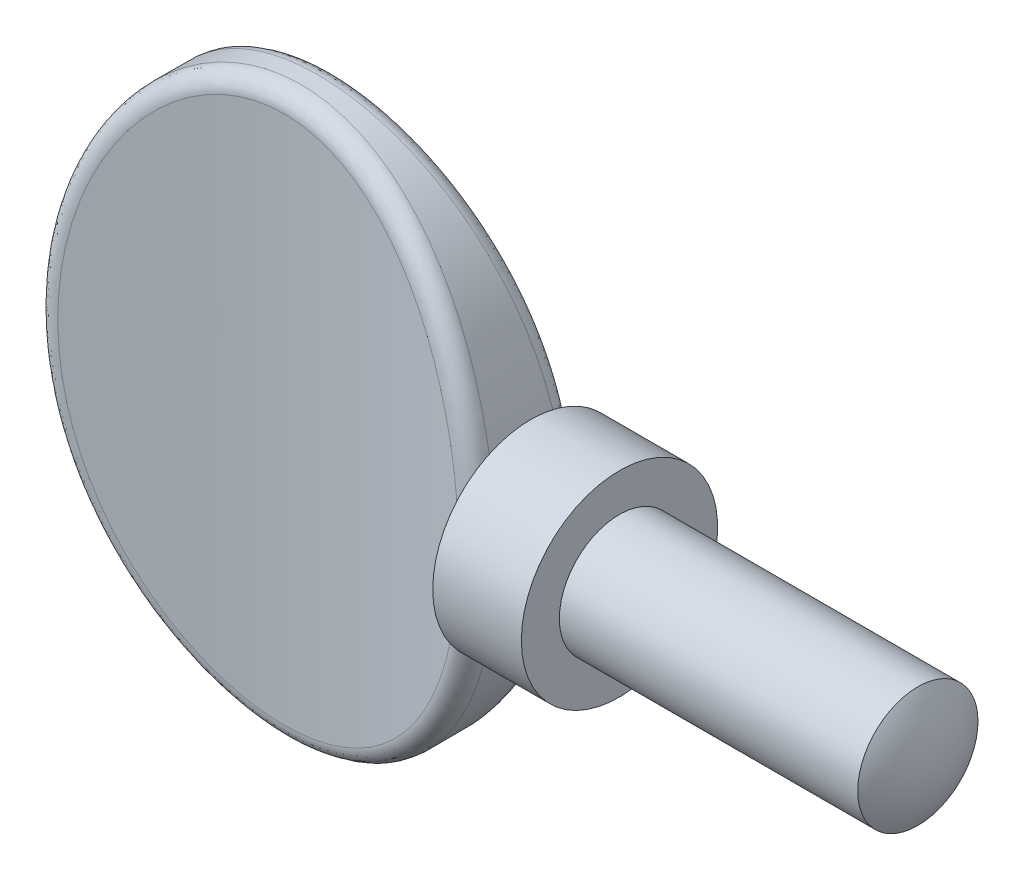
SolidWorks part; units mm, degrees
ref_plane "Front" through (0, 0, 0) normal (0, 0, 1) x (1, 0, 0)
ref_plane "Top" through (0, 0, 0) normal (0, 1, 0) x (1, 0, 0)
ref_plane "Right" through (0, 0, 0) normal (1, 0, 0) x (0, 0, -1)
ref_axis "Axis1" through (-50, 0, 0) along (1, 0, 0)
sketch "Sketch1" plane through (0, 0, 0) normal (0, 0, 1) x (1, 0, 0)
  line L0 (0, 0) -> (25.146, 0) construction
  line L1 (12.446, -3.937) -> (12.446, 3.937)
  ellipse E0 centre (0, 0) end of major axis (0, 11.303) minor radius 8.89
  dimension "D2" = 3.556
extrude "Extrude1" add sketch "Sketch1" along normal mid plane 4.572
sketch "Sketch2" plane through (0, 0, 0) normal (0, 1, 0) x (1, 0, 0)
  line L0 (8.89, 2.286) -> (-8.89, 2.286) construction
  line L1 (0, 0) -> (0, 1.1721) construction
  line L2 (-1.7991, 0) -> (2.0444, 0) construction
  line L3 (-8.89, -2.286) -> (8.89, -2.286) construction
  line L6 (-8.89, 2.286) -> (-8.89, -2.286)
  line L7 (8.89, 2.286) -> (8.89, -2.286)
  arc A0 (-8.89, 2.286) -> (8.89, 2.286) centre (0, 32.766) ccw
  arc A1 (-8.89, -2.286) -> (8.89, -2.286) centre (0, -32.766) cw
extrude "Cut-Extrude1" cut sketch "Sketch2" against normal through all and the other way through all flip side to cut
fillet "Fillet3" radius 0.6773 2 edges at (-8.875, -0.6558, 2.2816) (-1.5369, -11.1328, -1.0532)
sketch "Sketch3" plane through (0, 0, 0) normal (0, 1, 0) x (1, 0, 0)
  line L0 (12.446, 3.937) -> (12.446, 2.413)
  line L1 (0, 0) -> (21.0288, 0) construction
  line L2 (0, 0) -> (25.146, 0) construction
  line L3 (12.446, 2.413) -> (12.446, 0) construction
  line L4 (12.446, 2.413) -> (24.4192, 2.413)
  line L5 (25.146, 0) -> (25.146, -1.6666) construction
  line L6 (12.446, 3.937) -> (8.89, 3.937)
  line L7 (7.2364, 1.8517) -> (7.2364, 0)
  line L8 (8.89, 0) -> (8.89, 3.937) construction
  line L9 (7.2364, 0) -> (25.146, 0)
  arc A0 (8.89, 3.937) -> (7.2364, 1.8517) centre (6.7483, 3.937) cw
  arc A1 (25.146, 0) -> (24.4192, 2.413) centre (20.7772, 0) ccw
  arc A3 (-8.89, 2.286) -> (8.89, 2.286) centre (0, 32.766) ccw construction
  dimension "D1" = 7.874
revolve "Revolve1" add sketch "Sketch3" angle 360 about L0
cosmetic thread "Cosmetic Thread1" [suppressed]
sketch "Sketch4" plane through (0, 0, 0) normal (0, 0, 1) x (1, 0, 0)
  line L0 (0, 0) -> (27.7993, 0) construction
  line L1 (24.0555, 2.413) -> (24.4192, 1.7831)
  line L2 (24.4192, 1.7831) -> (24.7828, 2.413)
  line L3 (24.7828, 2.413) -> (24.7828, 3.1404)
  line L4 (24.7828, 3.1404) -> (24.0555, 3.1404)
  line L5 (24.0555, 3.1404) -> (24.0555, 2.413)
  line L6 (24.4192, 2.413) -> (24.4192, -2.413) construction
  dimension "D1" = 3.5662
  dimension "D2" = 4.826
revolve "Cut-Revolve10" [suppressed] cut sketch "Sketch4" angle 360 about L0
pattern_linear "LPattern10" [suppressed] count 11 along (-1, 0, 0) of bodies 109
equation "\"D2@Sketch1\" = \"B@Sketch1\" / 6"
equation "\"D1@Sketch3\" = \"E@Sketch1\""
equation "\"D1@Fillet3\" = \"C1@Sketch2\" / 3"
equation "\"D1@Sketch4\" = \"D2@Cosmetic Thread1\""
equation "\"D2@Sketch4\" = \"DIA@Sketch3\""
equation "\"D1@LPattern10\" = \"L@Sketch1\" / \"P@LPattern10\"  - 1"
